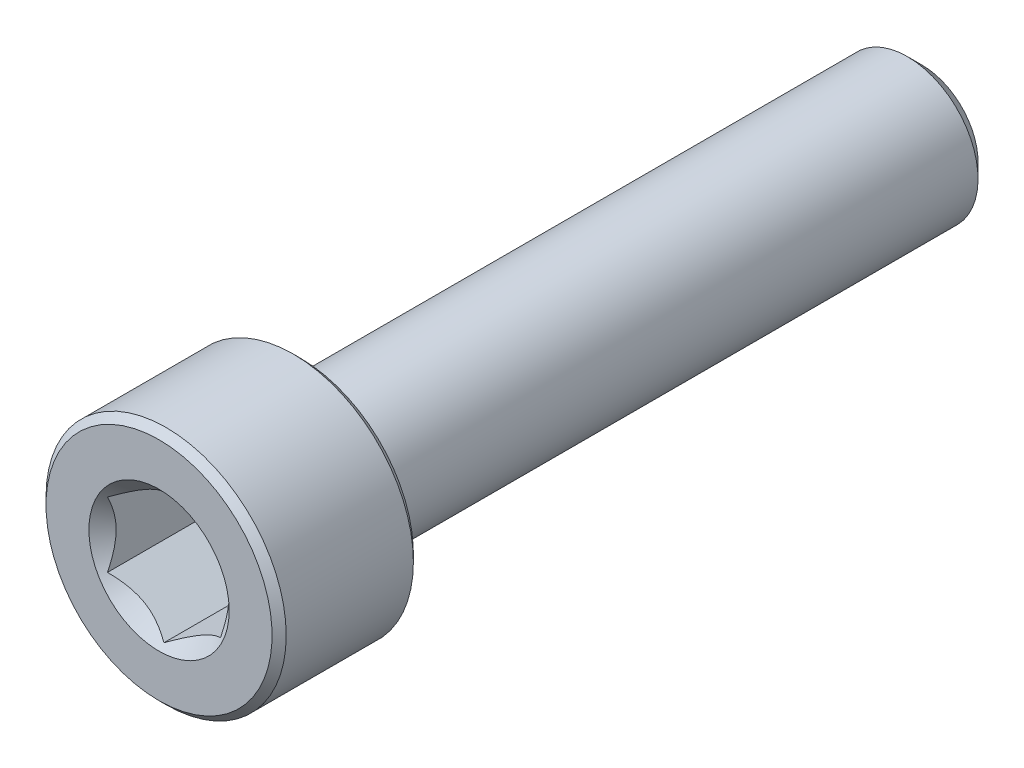
SolidWorks part; units mm, degrees
ref_plane "Front Plane" through (0, 0, 0) normal (0, 0, 1) x (1, 0, 0)
ref_plane "Top Plane" through (0, 0, 0) normal (0, 1, 0) x (1, 0, 0)
ref_plane "Right Plane" through (0, 0, 0) normal (1, 0, 0) x (0, 0, -1)
sketch "Sketch1" plane through (0, 0, 0) normal (1, 0, 0) x (0, 0, -1)
  line L0 (-13.5, 0) -> (13.5, 0) construction
  line L1 (13.5, 0) -> (13.5, 1.9804) construction
  line L2 (13.5, 1.9804) -> (12.9804, 2.5) construction
  line L3 (12.9804, 2.5) -> (12.9, 2.5) construction
  line L4 (12.9, 2.5) -> (-8.5, 2.5) construction
  line L5 (-8.5, 2.5) -> (-8.5, 4.25) construction
  line L6 (-8.5, 4.25) -> (-13.5, 4.25) construction
  line L7 (-13.5, 4.25) -> (-13.5, 0) construction
  line L8 (13.5, 1.9804) -> (13.5, 2.5) construction
  line L9 (13.45, 2.5866) -> (13.85, 1.8938) construction
  line L10 (13.85, 1.8938) -> (14.25, 2.5866) construction
  line L11 (14.25, 2.5866) -> (13.45, 2.5866) construction
  line L12 (13.85, 2.5866) -> (13.85, 2.5) construction
  line L13 (13.85, 1.8938) -> (13.85, 1.9804) construction
  line L14 (13.8, 1.9804) -> (13.9, 1.9804) construction
  line L15 (13.5, 2.5) -> (14.2, 2.5) construction
  line L16 (13.475, 2.5433) -> (14.225, 2.5433) construction
  line L17 (13.5, 0) -> (13.5, -2.5) construction
  line L18 (-8.75, 4.25) -> (-8.5, 4) construction
  line L19 (-13.25, 4.25) -> (-13.5, 4) construction
  line L20 (-8.5, 2.5) -> (-8.5, 0) construction
  line L21 (-8.5, 1.25) -> (-1.1667, 1.25) construction
  line L22 (-1.1667, 1.25) -> (6.1667, 1.25) construction
  line L23 (6.1667, 1.25) -> (13.5, 1.25) construction
  line L24 (-1.1667, 1.25) -> (-1.1667, 2.5) construction
  line L25 (-1.1667, 2.5) -> (-1.1667, 4.25) construction
  line L26 (6.1667, 1.25) -> (6.1667, 4.25) construction
  point P0 (-13.5, 2)
  point P3 (11.5, 2.5)
  point P4 (0, 0)
  point P18 (6.1667, 2.5)
  point P22 (13.85, 1.9804)
  point P24 (12.9, 2.5)
  point P25 (13.85, 2.5)
  point P28 (13.85, 2.5433)
  point P29 (11.5, -2.5)
  point P30 (-1.1667, 2.5)
  point P31 (-11, 4.25)
  point P37 (-9.375, 4.25)
  point P38 (-13.125, 4.25)
  point P45 (-1.1667, 1.25)
  point P46 (6.1667, 1.25)
  dimension "D2" = 0.1
  dimension "D7" = 0.25
  dimension "D8" = 0.25
  dimension "D9" = 0.25
  dimension "D10" = 0.125
  dimension "D11" = 0.625
  dimension "Drive Size" = 4
  dimension "Head Diameter" = 8.5
  dimension "Head Height" = 5
  dimension "Thread Pitch" = 0.8
  dimension "Thread Dia" = 5
  dimension "Length" = 22
  dimension "D12" = 0.6
  dimension "D4" = 2
  dimension "D3" = 45
sketch "Sketch2" plane through (0, 0, 0) normal (1, 0, 0) x (0, 0, -1)
  line L0 (-13.5, 0) -> (-13.5, 4)
  line L1 (-13.25, 4.25) -> (-8.75, 4.25)
  line L2 (-8.5, 4) -> (-8.5, 2.75)
  line L4 (12.9804, 2.5) -> (13.5, 1.9804)
  line L5 (13.5, 1.9804) -> (13.5, 0)
  line L6 (-8.5, 4.25) -> (-13.5, 4.25) construction
  line L7 (13.5, 0) -> (-13.5, 0)
  line L8 (-13.25, 4.25) -> (-13.5, 4) construction
  line L10 (-13.25, 4.25) -> (-13.5, 4)
  line L14 (-8.75, 4.25) -> (-8.5, 4) construction
  line L16 (-8.75, 4.25) -> (-8.5, 4)
  line L17 (-8.5, 2.5) -> (-8.5, 4.25) construction
  line L19 (-8.25, 2.5) -> (12.9804, 2.5)
  line L20 (12.9, 2.5) -> (-8.5, 2.5) construction
  arc A1 (-8.5, 2.75) -> (-8.25, 2.5) centre (-8.25, 2.75) ccw
  dimension "D3" = 0.25
revolve "Revolve1" add sketch "Sketch2" angle 360 about L7
sketch "Sketch3" plane through (0, 0, 13.5) normal (0, 0, 1) x (1, 0, 0)
  line L1 (2, -1.1547) -> (2, 1.1547)
  line L2 (2, 1.1547) -> (0, 2.3094)
  line L3 (0, 2.3094) -> (-2, 1.1547)
  line L4 (-2, 1.1547) -> (-2, -1.1547)
  line L5 (-2, -1.1547) -> (0, -2.3094)
  line L6 (0, -2.3094) -> (2, -1.1547)
  circle A0 centre (0, 0) radius 2 construction
  circle A1 centre (0, 0) radius 4.25 construction
  circle A2 centre (0, 0) radius 4.25 construction
  circle A3 centre (0, 0) radius 2.3094 construction
  point P13 (0, 0)
  dimension "D1" = 4.6188
extrude "Cut-Extrude1" cut sketch "Sketch3" against normal offset from surface (4 mm away) 1 up to face at (0, 4, 8.5)
sketch "Sketch4" plane through (0, 0, 13.5) normal (0, 0, 1) x (1, 0, 0)
  circle A0 centre (0, 0) radius 2.4826
  dimension "D1" = 4.9652
extrude "Cut-Extrude2" cut sketch "Sketch4" against normal up to vertex (2.5 mm away) draft 45 up to point (0, 4.25, 11)
sketch "Sketch11" plane through (0, 0, 0) normal (1, 0, 0) x (0, 0, -1)
  line L0 (-13.5, 0) -> (13.5, 0) construction
  line L1 (-13.5, 0) -> (13.5, 0) construction
  line L2 (-4.375, 0) -> (-4.375, 2.5) construction
  line L3 (12.9, 2.5) -> (-8.5, 2.5) construction
  line L4 (9.375, 0) -> (9.375, 2.5) construction
  line L6 (13.5, 1.9804) -> (13.5, 2.5) construction
  point P2 (-4.375, 0)
  point P3 (9.375, 0)
  dimension "D1" = 4.125
  dimension "D2" = 4.125
sketch "Sketch6" [suppressed] plane through (0, 0, -13.5) normal (0, 0, -1) x (-1, 0, 0)
  circle A0 centre (0, 0) radius 2.5
curve "Helix/Spiral1" [suppressed] pitch 0.8 height 22.8 turns 28.5
sketch "Sketch10" [suppressed] plane through (0, 0, 0) normal (1, 0, 0) x (0, 0, -1)
  line L0 (-8.25, -4.25) -> (-8.25, 4.25)
  line L5 (-13.5, 0) -> (13.5, 0) construction
  line L6 (-8.25, 2.5) -> (-8.25, -2.5) construction
  point P3 (-8.25, 0)
split "Split1" [suppressed] bodies to split 106
sketch "Sketch7" [suppressed] plane through (0, 0, 0) normal (1, 0, 0) x (0, 0, -1)
  line L0 (13.475, 2.5433) -> (14.225, 2.5433)
  line L1 (14.225, 2.5433) -> (13.9, 1.9804)
  line L2 (13.9, 1.9804) -> (13.8, 1.9804)
  line L3 (13.8, 1.9804) -> (13.475, 2.5433)
sweep "Cut-Sweep1" [suppressed] cut profiles "Sketch7" path "Helix/Spiral1"
sketch "Sketch8" [suppressed] plane through (0, 0, 0) normal (1, 0, 0) x (0, 0, -1)
  line L0 (-8.5, 0) -> (-8.5, 2.5)
  line L1 (-8.25, -2.5) -> (-8.25, 2.5) construction
  line L2 (-8.5, 2.5) -> (-8.25, 2.5)
  line L4 (-8.25, 2.5) -> (-6.8066, 0)
  line L5 (-6.8066, 0) -> (-8.5, 0)
  line L6 (12.9, 2.5) -> (-8.5, 2.5) construction
  line L7 (-13.5, 0) -> (13.5, 0) construction
  dimension "D1" = 60
revolve "Revolve2" [suppressed] add sketch "Sketch8" angle 360 about L5
equation "\"D2@Sketch1\" = \"Thread Pitch@Sketch1\" / 8"
equation "\"D4@Helix/Spiral1\" = \"Thread Pitch@Sketch1\""
equation "\"D7@Sketch1\" = \"Head Height@Sketch1\" * .05"
equation "\"D8@Sketch1\"=\"D7@Sketch1\""
equation "\"D9@Sketch1\"=\"D7@Sketch1\""
equation "\"D10@Sketch1\"=\"D7@Sketch1\"/2"
equation "\"D11@Sketch1\"=\"D10@Sketch1\"*5"
equation "\"D4@Sketch1\"=\"Thread Pitch@Sketch1\"*2.5"
equation "\"D12@Sketch1\"=\"Thread Pitch@Sketch1\"*.75"
equation "\"D3@Helix/Spiral1\"=\"Length@Sketch1\"+\"Thread Pitch@Sketch1\""
equation "\"D3@Sketch2\"=\"Thread Dia@Sketch1\"*0.05"
equation "\"D1@Sketch11\"=\"Length@Sketch1\"*0.1875"
equation "\"D2@Sketch11\"=\"D1@Sketch11\""
equation "\"D1@Sketch4\"=\"D1@Sketch3\"*1.075"
